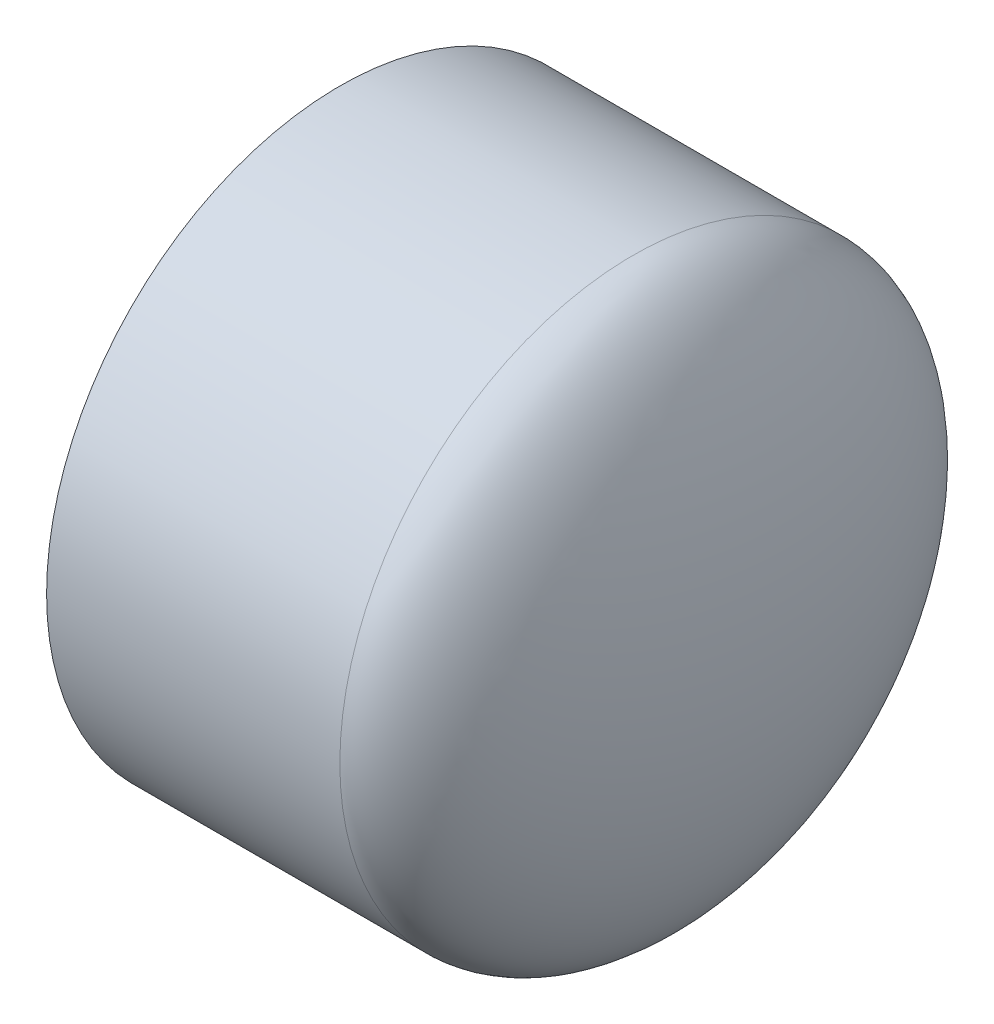
SolidWorks part; units mm, degrees
ref_plane "Front Plane" through (0, 0, 0) normal (0, 0, 1) x (1, 0, 0)
ref_plane "Top Plane" through (0, 0, 0) normal (0, 1, 0) x (1, 0, 0)
ref_plane "Right Plane" through (0, 0, 0) normal (1, 0, 0) x (0, 0, -1)
sketch "Sketch0" plane through (0, 0, 0) normal (0, 0, 1) x (1, 0, 0)
  line L0 (-52.832, 0) -> (0, 0) construction
  line L2 (-14.732, 0) -> (0, 0) construction
  line L4 (-52.832, 38.1) -> (-52.832, -38.1) construction
  line L5 (-14.732, 30.0863) -> (-52.832, 30.3149) construction
  line L6 (-14.732, 30.0863) -> (-14.732, -30.0863) construction
  line L7 (-14.732, -30.0863) -> (-52.832, -30.3149) construction
  line L8 (-52.832, 30.3149) -> (-52.832, -30.3149) construction
  line L14 (-14.732, 24.6253) -> (-14.732, -24.6253) construction
  dimension "M" = 76.2
  dimension "OD A" = 60.6298
  dimension "OD B" = 60.1726
  dimension "ID" = 49.2506
  dimension "W" = 52.832
  dimension "C" = 38.1
sketch "Sketch1" plane through (0, 0, 0) normal (0, 0, 1) x (1, 0, 0)
  line L0 (-52.832, 0) -> (0, 0) construction
  line L1 (-52.832, 0) -> (0, 0) construction
  line L2 (-14.732, 0) -> (0, 0) construction
  line L3 (-52.832, -38.1) -> (-14.732, -38.1)
  line L4 (-52.832, -38.1) -> (-52.832, -30.3149)
  line L5 (-52.832, -30.3149) -> (-14.732, -30.0863)
  line L6 (-14.732, 0) -> (-14.732, -30.0863) construction
  line L7 (-14.732, -30.0863) -> (-14.732, -38.1) construction
  line L8 (-8.0137, 0) -> (0, 0)
  ellipse E0 centre (-14.732, 0) end of major axis (-14.732, 38.1) minor radius 14.732 (-14.732, -38.1) -> (0, 0) ccw
  ellipse E1 centre (-14.732, 0) end of major axis (-14.732, -30.0863) minor radius 6.7183 (-14.732, -30.0863) -> (-8.0137, 0) ccw
revolve "Revolve1" add sketch "Sketch1" angle 360 about L1
other "CPoint1" parameters "Diameter"=50.8, "StubLength"=114.3
ref_axis "Axis1" through (-24.732, 0, 0) along (1, 0, 0)
other "RPoint1"
